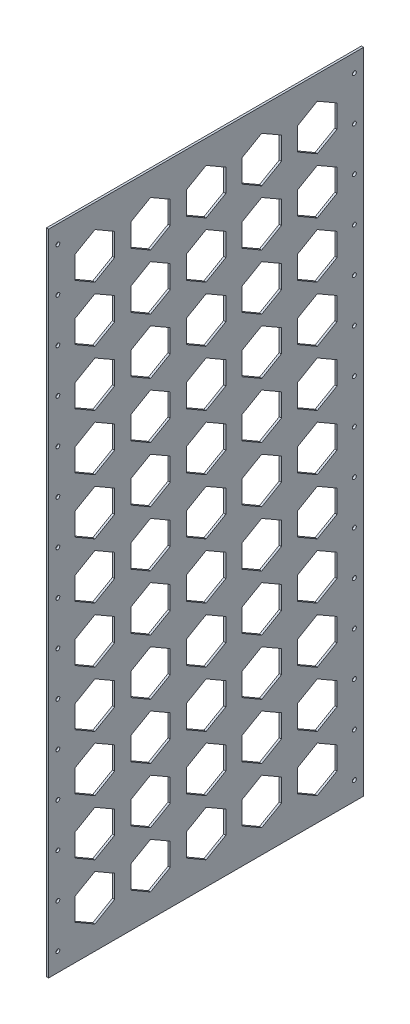
SolidWorks part; units mm, degrees
ref_plane "Front" through (0, 0, 0) normal (0, 0, 1) x (1, 0, 0)
ref_plane "Top" through (0, 0, 0) normal (0, 1, 0) x (1, 0, 0)
ref_plane "Right" through (0, 0, 0) normal (1, 0, 0) x (0, 0, -1)
sketch "Sketch1" plane through (0, 0, 0) normal (1, 0, 0) x (0, 0, -1)
  line L1 (0, 0) -> (431.8, 0)
  line L2 (0, 0) -> (0, 889)
  line L3 (0, 889) -> (431.8, 889)
  line L4 (431.8, 0) -> (431.8, 889)
  dimension "D1" = 889
  dimension "D2" = 431.8
extrude "Boss-Extrude1" add sketch "Sketch1" along normal blind 3
sketch "Sketch2" plane through (3, 0, 0) normal (1, 0, 0) x (0, 0, -1)
  line L1 (0, 0) -> (431.8, 0) construction
  line L2 (12.7, 25.4) -> (419.1, 25.4) construction
  line L3 (12.7, 25.4) -> (0, 25.4) construction
  line L4 (0, 889) -> (0, 0) construction
  line L5 (419.1, 25.4) -> (431.8, 25.4) construction
  line L6 (431.8, 0) -> (431.8, 889) construction
  line L7 (215.9, 25.4) -> (215.9, 0) construction
  circle A0 centre (12.7, 25.4) radius 2.667
  circle A1 centre (419.1, 25.4) radius 2.667
  circle A2 centre (419.1, 85.344) radius 2.667
  circle A3 centre (419.1, 145.288) radius 2.667
  circle A4 centre (419.1, 205.232) radius 2.667
  circle A5 centre (419.1, 265.176) radius 2.667
  circle A6 centre (419.1, 325.12) radius 2.667
  circle A7 centre (419.1, 385.064) radius 2.667
  circle A8 centre (419.1, 445.008) radius 2.667
  circle A9 centre (419.1, 504.952) radius 2.667
  circle A10 centre (419.1, 564.896) radius 2.667
  circle A11 centre (12.7, 85.344) radius 2.667
  circle A12 centre (12.7, 145.288) radius 2.667
  circle A13 centre (12.7, 205.232) radius 2.667
  circle A14 centre (12.7, 265.176) radius 2.667
  circle A15 centre (12.7, 325.12) radius 2.667
  circle A16 centre (12.7, 385.064) radius 2.667
  circle A17 centre (12.7, 445.008) radius 2.667
  circle A18 centre (12.7, 504.952) radius 2.667
  circle A19 centre (12.7, 564.896) radius 2.667
  circle A20 centre (12.7, 624.84) radius 2.667
  circle A21 centre (419.1, 624.84) radius 2.667
  circle A22 centre (12.7, 684.784) radius 2.667
  circle A23 centre (419.1, 684.784) radius 2.667
  circle A24 centre (12.7, 744.728) radius 2.667
  circle A25 centre (419.1, 744.728) radius 2.667
  circle A26 centre (12.7, 804.672) radius 2.667
  circle A27 centre (419.1, 804.672) radius 2.667
  circle A28 centre (12.7, 864.616) radius 2.667
  circle A29 centre (419.1, 864.616) radius 2.667
  dimension "D3" = 5.334
  dimension "D1" = 25.4
  dimension "D2" = 406.4
  dimension "D4" = 2
  dimension "D5" = 15
extrude "Cut-Extrude1" cut sketch "Sketch2" against normal up to next (3 mm away)
sketch "Sketch3" plane through (3, 0, 0) normal (1, 0, 0) x (0, 0, -1)
  line L0 (112.6706, 47.8946) -> (139.7, 32.2891)
  line L1 (36.4706, 47.8946) -> (63.5, 32.2891)
  line L2 (63.5, 32.2891) -> (90.5294, 47.8946)
  line L3 (90.5294, 47.8946) -> (90.5294, 79.1054)
  line L4 (90.5294, 79.1054) -> (63.5, 94.7109)
  line L5 (63.5, 94.7109) -> (36.4706, 79.1054)
  line L6 (36.4706, 79.1054) -> (36.4706, 47.8946)
  line L7 (139.7, 32.2891) -> (166.7294, 47.8946)
  line L8 (166.7294, 47.8946) -> (166.7294, 79.1054)
  line L9 (166.7294, 79.1054) -> (139.7, 94.7109)
  line L10 (139.7, 94.7109) -> (112.6706, 79.1054)
  line L11 (112.6706, 79.1054) -> (112.6706, 47.8946)
  line L12 (188.8706, 47.8946) -> (215.9, 32.2891)
  line L13 (215.9, 32.2891) -> (242.9294, 47.8946)
  line L14 (242.9294, 47.8946) -> (242.9294, 79.1054)
  line L15 (242.9294, 79.1054) -> (215.9, 94.7109)
  line L16 (215.9, 94.7109) -> (188.8706, 79.1054)
  line L17 (188.8706, 79.1054) -> (188.8706, 47.8946)
  line L18 (265.0706, 47.8946) -> (292.1, 32.2891)
  line L19 (292.1, 32.2891) -> (319.1294, 47.8946)
  line L20 (319.1294, 47.8946) -> (319.1294, 79.1054)
  line L21 (319.1294, 79.1054) -> (292.1, 94.7109)
  line L22 (292.1, 94.7109) -> (265.0706, 79.1054)
  line L23 (265.0706, 79.1054) -> (265.0706, 47.8946)
  line L24 (341.2706, 47.8946) -> (368.3, 32.2891)
  line L25 (368.3, 32.2891) -> (395.3294, 47.8946)
  line L26 (395.3294, 47.8946) -> (395.3294, 79.1054)
  line L27 (395.3294, 79.1054) -> (368.3, 94.7109)
  line L28 (368.3, 94.7109) -> (341.2706, 79.1054)
  line L29 (341.2706, 79.1054) -> (341.2706, 47.8946)
  line L30 (112.6706, 124.0946) -> (139.7, 108.4891)
  line L31 (139.7, 108.4891) -> (166.7294, 124.0946)
  line L32 (166.7294, 124.0946) -> (166.7294, 155.3054)
  line L33 (166.7294, 155.3054) -> (139.7, 170.9109)
  line L34 (139.7, 170.9109) -> (112.6706, 155.3054)
  line L35 (112.6706, 155.3054) -> (112.6706, 124.0946)
  line L36 (188.8706, 124.0946) -> (215.9, 108.4891)
  line L37 (215.9, 108.4891) -> (242.9294, 124.0946)
  line L38 (242.9294, 124.0946) -> (242.9294, 155.3054)
  line L39 (242.9294, 155.3054) -> (215.9, 170.9109)
  line L40 (215.9, 170.9109) -> (188.8706, 155.3054)
  line L41 (188.8706, 155.3054) -> (188.8706, 124.0946)
  line L42 (265.0706, 124.0946) -> (292.1, 108.4891)
  line L43 (292.1, 108.4891) -> (319.1294, 124.0946)
  line L44 (319.1294, 124.0946) -> (319.1294, 155.3054)
  line L45 (319.1294, 155.3054) -> (292.1, 170.9109)
  line L46 (292.1, 170.9109) -> (265.0706, 155.3054)
  line L47 (265.0706, 155.3054) -> (265.0706, 124.0946)
  line L48 (341.2706, 124.0946) -> (368.3, 108.4891)
  line L49 (368.3, 108.4891) -> (395.3294, 124.0946)
  line L50 (395.3294, 124.0946) -> (395.3294, 155.3054)
  line L51 (395.3294, 155.3054) -> (368.3, 170.9109)
  line L52 (368.3, 170.9109) -> (341.2706, 155.3054)
  line L53 (341.2706, 155.3054) -> (341.2706, 124.0946)
  line L54 (112.6706, 200.2946) -> (139.7, 184.6891)
  line L55 (139.7, 184.6891) -> (166.7294, 200.2946)
  line L56 (166.7294, 200.2946) -> (166.7294, 231.5054)
  line L57 (166.7294, 231.5054) -> (139.7, 247.1109)
  line L58 (139.7, 247.1109) -> (112.6706, 231.5054)
  line L59 (112.6706, 231.5054) -> (112.6706, 200.2946)
  line L60 (188.8706, 200.2946) -> (215.9, 184.6891)
  line L61 (215.9, 184.6891) -> (242.9294, 200.2946)
  line L62 (242.9294, 200.2946) -> (242.9294, 231.5054)
  line L63 (242.9294, 231.5054) -> (215.9, 247.1109)
  line L64 (215.9, 247.1109) -> (188.8706, 231.5054)
  line L65 (188.8706, 231.5054) -> (188.8706, 200.2946)
  line L66 (265.0706, 200.2946) -> (292.1, 184.6891)
  line L67 (292.1, 184.6891) -> (319.1294, 200.2946)
  line L68 (319.1294, 200.2946) -> (319.1294, 231.5054)
  line L69 (319.1294, 231.5054) -> (292.1, 247.1109)
  line L70 (292.1, 247.1109) -> (265.0706, 231.5054)
  line L71 (265.0706, 231.5054) -> (265.0706, 200.2946)
  line L72 (341.2706, 200.2946) -> (368.3, 184.6891)
  line L73 (368.3, 184.6891) -> (395.3294, 200.2946)
  line L74 (395.3294, 200.2946) -> (395.3294, 231.5054)
  line L75 (395.3294, 231.5054) -> (368.3, 247.1109)
  line L76 (368.3, 247.1109) -> (341.2706, 231.5054)
  line L77 (341.2706, 231.5054) -> (341.2706, 200.2946)
  line L78 (112.6706, 276.4946) -> (139.7, 260.8891)
  line L79 (139.7, 260.8891) -> (166.7294, 276.4946)
  line L80 (166.7294, 276.4946) -> (166.7294, 307.7054)
  line L81 (166.7294, 307.7054) -> (139.7, 323.3109)
  line L82 (139.7, 323.3109) -> (112.6706, 307.7054)
  line L83 (112.6706, 307.7054) -> (112.6706, 276.4946)
  line L84 (188.8706, 276.4946) -> (215.9, 260.8891)
  line L85 (215.9, 260.8891) -> (242.9294, 276.4946)
  line L86 (242.9294, 276.4946) -> (242.9294, 307.7054)
  line L87 (242.9294, 307.7054) -> (215.9, 323.3109)
  line L88 (215.9, 323.3109) -> (188.8706, 307.7054)
  line L89 (188.8706, 307.7054) -> (188.8706, 276.4946)
  line L90 (265.0706, 276.4946) -> (292.1, 260.8891)
  line L91 (292.1, 260.8891) -> (319.1294, 276.4946)
  line L92 (319.1294, 276.4946) -> (319.1294, 307.7054)
  line L93 (319.1294, 307.7054) -> (292.1, 323.3109)
  line L94 (292.1, 323.3109) -> (265.0706, 307.7054)
  line L95 (265.0706, 307.7054) -> (265.0706, 276.4946)
  line L96 (341.2706, 276.4946) -> (368.3, 260.8891)
  line L97 (368.3, 260.8891) -> (395.3294, 276.4946)
  line L98 (395.3294, 276.4946) -> (395.3294, 307.7054)
  line L99 (395.3294, 307.7054) -> (368.3, 323.3109)
  line L100 (368.3, 323.3109) -> (341.2706, 307.7054)
  line L101 (341.2706, 307.7054) -> (341.2706, 276.4946)
  line L102 (112.6706, 352.6946) -> (139.7, 337.0891)
  line L103 (139.7, 337.0891) -> (166.7294, 352.6946)
  line L104 (166.7294, 352.6946) -> (166.7294, 383.9054)
  line L105 (166.7294, 383.9054) -> (139.7, 399.5109)
  line L106 (139.7, 399.5109) -> (112.6706, 383.9054)
  line L107 (112.6706, 383.9054) -> (112.6706, 352.6946)
  line L108 (188.8706, 352.6946) -> (215.9, 337.0891)
  line L109 (215.9, 337.0891) -> (242.9294, 352.6946)
  line L110 (242.9294, 352.6946) -> (242.9294, 383.9054)
  line L111 (242.9294, 383.9054) -> (215.9, 399.5109)
  line L112 (215.9, 399.5109) -> (188.8706, 383.9054)
  line L113 (188.8706, 383.9054) -> (188.8706, 352.6946)
  line L114 (265.0706, 352.6946) -> (292.1, 337.0891)
  line L115 (292.1, 337.0891) -> (319.1294, 352.6946)
  line L116 (319.1294, 352.6946) -> (319.1294, 383.9054)
  line L117 (319.1294, 383.9054) -> (292.1, 399.5109)
  line L118 (292.1, 399.5109) -> (265.0706, 383.9054)
  line L119 (265.0706, 383.9054) -> (265.0706, 352.6946)
  line L120 (341.2706, 352.6946) -> (368.3, 337.0891)
  line L121 (368.3, 337.0891) -> (395.3294, 352.6946)
  line L122 (395.3294, 352.6946) -> (395.3294, 383.9054)
  line L123 (395.3294, 383.9054) -> (368.3, 399.5109)
  line L124 (368.3, 399.5109) -> (341.2706, 383.9054)
  line L125 (341.2706, 383.9054) -> (341.2706, 352.6946)
  line L126 (112.6706, 428.8946) -> (139.7, 413.2891)
  line L127 (139.7, 413.2891) -> (166.7294, 428.8946)
  line L128 (166.7294, 428.8946) -> (166.7294, 460.1054)
  line L129 (166.7294, 460.1054) -> (139.7, 475.7109)
  line L130 (139.7, 475.7109) -> (112.6706, 460.1054)
  line L131 (112.6706, 460.1054) -> (112.6706, 428.8946)
  line L132 (188.8706, 428.8946) -> (215.9, 413.2891)
  line L133 (215.9, 413.2891) -> (242.9294, 428.8946)
  line L134 (242.9294, 428.8946) -> (242.9294, 460.1054)
  line L135 (242.9294, 460.1054) -> (215.9, 475.7109)
  line L136 (215.9, 475.7109) -> (188.8706, 460.1054)
  line L137 (188.8706, 460.1054) -> (188.8706, 428.8946)
  line L138 (265.0706, 428.8946) -> (292.1, 413.2891)
  line L139 (292.1, 413.2891) -> (319.1294, 428.8946)
  line L140 (319.1294, 428.8946) -> (319.1294, 460.1054)
  line L141 (319.1294, 460.1054) -> (292.1, 475.7109)
  line L142 (292.1, 475.7109) -> (265.0706, 460.1054)
  line L143 (265.0706, 460.1054) -> (265.0706, 428.8946)
  line L144 (341.2706, 428.8946) -> (368.3, 413.2891)
  line L145 (368.3, 413.2891) -> (395.3294, 428.8946)
  line L146 (395.3294, 428.8946) -> (395.3294, 460.1054)
  line L147 (395.3294, 460.1054) -> (368.3, 475.7109)
  line L148 (368.3, 475.7109) -> (341.2706, 460.1054)
  line L149 (341.2706, 460.1054) -> (341.2706, 428.8946)
  line L150 (112.6706, 505.0946) -> (139.7, 489.4891)
  line L151 (139.7, 489.4891) -> (166.7294, 505.0946)
  line L152 (166.7294, 505.0946) -> (166.7294, 536.3054)
  line L153 (166.7294, 536.3054) -> (139.7, 551.9109)
  line L154 (139.7, 551.9109) -> (112.6706, 536.3054)
  line L155 (112.6706, 536.3054) -> (112.6706, 505.0946)
  line L156 (188.8706, 505.0946) -> (215.9, 489.4891)
  line L157 (215.9, 489.4891) -> (242.9294, 505.0946)
  line L158 (242.9294, 505.0946) -> (242.9294, 536.3054)
  line L159 (242.9294, 536.3054) -> (215.9, 551.9109)
  line L160 (215.9, 551.9109) -> (188.8706, 536.3054)
  line L161 (188.8706, 536.3054) -> (188.8706, 505.0946)
  line L162 (265.0706, 505.0946) -> (292.1, 489.4891)
  line L163 (292.1, 489.4891) -> (319.1294, 505.0946)
  line L164 (319.1294, 505.0946) -> (319.1294, 536.3054)
  line L165 (319.1294, 536.3054) -> (292.1, 551.9109)
  line L166 (292.1, 551.9109) -> (265.0706, 536.3054)
  line L167 (265.0706, 536.3054) -> (265.0706, 505.0946)
  line L168 (341.2706, 505.0946) -> (368.3, 489.4891)
  line L169 (368.3, 489.4891) -> (395.3294, 505.0946)
  line L170 (395.3294, 505.0946) -> (395.3294, 536.3054)
  line L171 (395.3294, 536.3054) -> (368.3, 551.9109)
  line L172 (368.3, 551.9109) -> (341.2706, 536.3054)
  line L173 (341.2706, 536.3054) -> (341.2706, 505.0946)
  line L174 (112.6706, 581.2946) -> (139.7, 565.6891)
  line L175 (139.7, 565.6891) -> (166.7294, 581.2946)
  line L176 (166.7294, 581.2946) -> (166.7294, 612.5054)
  line L177 (166.7294, 612.5054) -> (139.7, 628.1109)
  line L178 (139.7, 628.1109) -> (112.6706, 612.5054)
  line L179 (112.6706, 612.5054) -> (112.6706, 581.2946)
  line L180 (188.8706, 581.2946) -> (215.9, 565.6891)
  line L181 (215.9, 565.6891) -> (242.9294, 581.2946)
  line L182 (242.9294, 581.2946) -> (242.9294, 612.5054)
  line L183 (242.9294, 612.5054) -> (215.9, 628.1109)
  line L184 (215.9, 628.1109) -> (188.8706, 612.5054)
  line L185 (188.8706, 612.5054) -> (188.8706, 581.2946)
  line L186 (265.0706, 581.2946) -> (292.1, 565.6891)
  line L187 (292.1, 565.6891) -> (319.1294, 581.2946)
  line L188 (319.1294, 581.2946) -> (319.1294, 612.5054)
  line L189 (319.1294, 612.5054) -> (292.1, 628.1109)
  line L190 (292.1, 628.1109) -> (265.0706, 612.5054)
  line L191 (265.0706, 612.5054) -> (265.0706, 581.2946)
  line L192 (341.2706, 581.2946) -> (368.3, 565.6891)
  line L193 (368.3, 565.6891) -> (395.3294, 581.2946)
  line L194 (395.3294, 581.2946) -> (395.3294, 612.5054)
  line L195 (395.3294, 612.5054) -> (368.3, 628.1109)
  line L196 (368.3, 628.1109) -> (341.2706, 612.5054)
  line L197 (341.2706, 612.5054) -> (341.2706, 581.2946)
  line L198 (112.6706, 657.4946) -> (139.7, 641.8891)
  line L199 (139.7, 641.8891) -> (166.7294, 657.4946)
  line L200 (166.7294, 657.4946) -> (166.7294, 688.7054)
  line L201 (166.7294, 688.7054) -> (139.7, 704.3109)
  line L202 (139.7, 704.3109) -> (112.6706, 688.7054)
  line L203 (112.6706, 688.7054) -> (112.6706, 657.4946)
  line L204 (188.8706, 657.4946) -> (215.9, 641.8891)
  line L205 (215.9, 641.8891) -> (242.9294, 657.4946)
  line L206 (242.9294, 657.4946) -> (242.9294, 688.7054)
  line L207 (242.9294, 688.7054) -> (215.9, 704.3109)
  line L208 (215.9, 704.3109) -> (188.8706, 688.7054)
  line L209 (188.8706, 688.7054) -> (188.8706, 657.4946)
  line L210 (265.0706, 657.4946) -> (292.1, 641.8891)
  line L211 (292.1, 641.8891) -> (319.1294, 657.4946)
  line L212 (319.1294, 657.4946) -> (319.1294, 688.7054)
  line L213 (319.1294, 688.7054) -> (292.1, 704.3109)
  line L214 (292.1, 704.3109) -> (265.0706, 688.7054)
  line L215 (265.0706, 688.7054) -> (265.0706, 657.4946)
  line L216 (341.2706, 657.4946) -> (368.3, 641.8891)
  line L217 (368.3, 641.8891) -> (395.3294, 657.4946)
  line L218 (395.3294, 657.4946) -> (395.3294, 688.7054)
  line L219 (395.3294, 688.7054) -> (368.3, 704.3109)
  line L220 (368.3, 704.3109) -> (341.2706, 688.7054)
  line L221 (341.2706, 688.7054) -> (341.2706, 657.4946)
  line L222 (112.6706, 733.6946) -> (139.7, 718.0891)
  line L223 (139.7, 718.0891) -> (166.7294, 733.6946)
  line L224 (166.7294, 733.6946) -> (166.7294, 764.9054)
  line L225 (166.7294, 764.9054) -> (139.7, 780.5109)
  line L226 (139.7, 780.5109) -> (112.6706, 764.9054)
  line L227 (112.6706, 764.9054) -> (112.6706, 733.6946)
  line L228 (188.8706, 733.6946) -> (215.9, 718.0891)
  line L229 (215.9, 718.0891) -> (242.9294, 733.6946)
  line L230 (242.9294, 733.6946) -> (242.9294, 764.9054)
  line L231 (242.9294, 764.9054) -> (215.9, 780.5109)
  line L232 (215.9, 780.5109) -> (188.8706, 764.9054)
  line L233 (188.8706, 764.9054) -> (188.8706, 733.6946)
  line L234 (265.0706, 733.6946) -> (292.1, 718.0891)
  line L235 (292.1, 718.0891) -> (319.1294, 733.6946)
  line L236 (319.1294, 733.6946) -> (319.1294, 764.9054)
  line L237 (319.1294, 764.9054) -> (292.1, 780.5109)
  line L238 (292.1, 780.5109) -> (265.0706, 764.9054)
  line L239 (265.0706, 764.9054) -> (265.0706, 733.6946)
  line L240 (341.2706, 733.6946) -> (368.3, 718.0891)
  line L241 (368.3, 718.0891) -> (395.3294, 733.6946)
  line L242 (395.3294, 733.6946) -> (395.3294, 764.9054)
  line L243 (395.3294, 764.9054) -> (368.3, 780.5109)
  line L244 (368.3, 780.5109) -> (341.2706, 764.9054)
  line L245 (341.2706, 764.9054) -> (341.2706, 733.6946)
  line L246 (112.6706, 809.8946) -> (139.7, 794.2891)
  line L247 (139.7, 794.2891) -> (166.7294, 809.8946)
  line L248 (166.7294, 809.8946) -> (166.7294, 841.1054)
  line L249 (166.7294, 841.1054) -> (139.7, 856.7109)
  line L250 (139.7, 856.7109) -> (112.6706, 841.1054)
  line L251 (112.6706, 841.1054) -> (112.6706, 809.8946)
  line L252 (188.8706, 809.8946) -> (215.9, 794.2891)
  line L253 (215.9, 794.2891) -> (242.9294, 809.8946)
  line L254 (242.9294, 809.8946) -> (242.9294, 841.1054)
  line L255 (242.9294, 841.1054) -> (215.9, 856.7109)
  line L256 (215.9, 856.7109) -> (188.8706, 841.1054)
  line L257 (188.8706, 841.1054) -> (188.8706, 809.8946)
  line L258 (265.0706, 809.8946) -> (292.1, 794.2891)
  line L259 (292.1, 794.2891) -> (319.1294, 809.8946)
  line L260 (319.1294, 809.8946) -> (319.1294, 841.1054)
  line L261 (319.1294, 841.1054) -> (292.1, 856.7109)
  line L262 (292.1, 856.7109) -> (265.0706, 841.1054)
  line L263 (265.0706, 841.1054) -> (265.0706, 809.8946)
  line L264 (341.2706, 809.8946) -> (368.3, 794.2891)
  line L265 (368.3, 794.2891) -> (395.3294, 809.8946)
  line L266 (395.3294, 809.8946) -> (395.3294, 841.1054)
  line L267 (395.3294, 841.1054) -> (368.3, 856.7109)
  line L268 (368.3, 856.7109) -> (341.2706, 841.1054)
  line L269 (341.2706, 841.1054) -> (341.2706, 809.8946)
  line L270 (36.4706, 124.0946) -> (63.5, 108.4891)
  line L271 (63.5, 108.4891) -> (90.5294, 124.0946)
  line L272 (90.5294, 124.0946) -> (90.5294, 155.3054)
  line L273 (90.5294, 155.3054) -> (63.5, 170.9109)
  line L274 (63.5, 170.9109) -> (36.4706, 155.3054)
  line L275 (36.4706, 155.3054) -> (36.4706, 124.0946)
  line L276 (36.4706, 200.2946) -> (63.5, 184.6891)
  line L277 (63.5, 184.6891) -> (90.5294, 200.2946)
  line L278 (90.5294, 200.2946) -> (90.5294, 231.5054)
  line L279 (90.5294, 231.5054) -> (63.5, 247.1109)
  line L280 (63.5, 247.1109) -> (36.4706, 231.5054)
  line L281 (36.4706, 231.5054) -> (36.4706, 200.2946)
  line L282 (36.4706, 276.4946) -> (63.5, 260.8891)
  line L283 (63.5, 260.8891) -> (90.5294, 276.4946)
  line L284 (90.5294, 276.4946) -> (90.5294, 307.7054)
  line L285 (90.5294, 307.7054) -> (63.5, 323.3109)
  line L286 (63.5, 323.3109) -> (36.4706, 307.7054)
  line L287 (36.4706, 307.7054) -> (36.4706, 276.4946)
  line L288 (36.4706, 352.6946) -> (63.5, 337.0891)
  line L289 (63.5, 337.0891) -> (90.5294, 352.6946)
  line L290 (90.5294, 352.6946) -> (90.5294, 383.9054)
  line L291 (90.5294, 383.9054) -> (63.5, 399.5109)
  line L292 (63.5, 399.5109) -> (36.4706, 383.9054)
  line L293 (36.4706, 383.9054) -> (36.4706, 352.6946)
  line L294 (36.4706, 428.8946) -> (63.5, 413.2891)
  line L295 (63.5, 413.2891) -> (90.5294, 428.8946)
  line L296 (90.5294, 428.8946) -> (90.5294, 460.1054)
  line L297 (90.5294, 460.1054) -> (63.5, 475.7109)
  line L298 (63.5, 475.7109) -> (36.4706, 460.1054)
  line L299 (36.4706, 460.1054) -> (36.4706, 428.8946)
  line L300 (36.4706, 505.0946) -> (63.5, 489.4891)
  line L301 (63.5, 489.4891) -> (90.5294, 505.0946)
  line L302 (90.5294, 505.0946) -> (90.5294, 536.3054)
  line L303 (90.5294, 536.3054) -> (63.5, 551.9109)
  line L304 (63.5, 551.9109) -> (36.4706, 536.3054)
  line L305 (36.4706, 536.3054) -> (36.4706, 505.0946)
  line L306 (36.4706, 581.2946) -> (63.5, 565.6891)
  line L307 (63.5, 565.6891) -> (90.5294, 581.2946)
  line L308 (90.5294, 581.2946) -> (90.5294, 612.5054)
  line L309 (90.5294, 612.5054) -> (63.5, 628.1109)
  line L310 (63.5, 628.1109) -> (36.4706, 612.5054)
  line L311 (36.4706, 612.5054) -> (36.4706, 581.2946)
  line L312 (36.4706, 657.4946) -> (63.5, 641.8891)
  line L313 (63.5, 641.8891) -> (90.5294, 657.4946)
  line L314 (90.5294, 657.4946) -> (90.5294, 688.7054)
  line L315 (90.5294, 688.7054) -> (63.5, 704.3109)
  line L316 (63.5, 704.3109) -> (36.4706, 688.7054)
  line L317 (36.4706, 688.7054) -> (36.4706, 657.4946)
  line L318 (36.4706, 733.6946) -> (63.5, 718.0891)
  line L319 (63.5, 718.0891) -> (90.5294, 733.6946)
  line L320 (90.5294, 733.6946) -> (90.5294, 764.9054)
  line L321 (90.5294, 764.9054) -> (63.5, 780.5109)
  line L322 (63.5, 780.5109) -> (36.4706, 764.9054)
  line L323 (36.4706, 764.9054) -> (36.4706, 733.6946)
  line L324 (36.4706, 809.8946) -> (63.5, 794.2891)
  line L325 (63.5, 794.2891) -> (90.5294, 809.8946)
  line L326 (90.5294, 809.8946) -> (90.5294, 841.1054)
  line L327 (90.5294, 841.1054) -> (63.5, 856.7109)
  line L328 (63.5, 856.7109) -> (36.4706, 841.1054)
  line L329 (36.4706, 841.1054) -> (36.4706, 809.8946)
  line L330 (63.5, 63.5) -> (0, 63.5) construction
  line L331 (0, 889) -> (0, 0) construction
  line L332 (368.3, 63.5) -> (431.8, 63.5) construction
  line L333 (431.8, 0) -> (431.8, 889) construction
  line L334 (63.5, 63.5) -> (63.5, 0) construction
  line L335 (0, 0) -> (431.8, 0) construction
  line L336 (63.5, 825.5) -> (63.5, 889) construction
  line L337 (431.8, 889) -> (0, 889) construction
  circle A0 centre (63.5, 63.5) radius 27.0294 construction
  circle A1 centre (139.7, 63.5) radius 27.0294 construction
  circle A2 centre (215.9, 63.5) radius 27.0294 construction
  circle A3 centre (292.1, 63.5) radius 27.0294 construction
  circle A4 centre (368.3, 63.5) radius 27.0294 construction
  circle A5 centre (139.7, 139.7) radius 27.0294 construction
  circle A6 centre (215.9, 139.7) radius 27.0294 construction
  circle A7 centre (292.1, 139.7) radius 27.0294 construction
  circle A8 centre (368.3, 139.7) radius 27.0294 construction
  circle A9 centre (139.7, 215.9) radius 27.0294 construction
  circle A10 centre (215.9, 215.9) radius 27.0294 construction
  circle A11 centre (292.1, 215.9) radius 27.0294 construction
  circle A12 centre (368.3, 215.9) radius 27.0294 construction
  circle A13 centre (139.7, 292.1) radius 27.0294 construction
  circle A14 centre (215.9, 292.1) radius 27.0294 construction
  circle A15 centre (292.1, 292.1) radius 27.0294 construction
  circle A16 centre (368.3, 292.1) radius 27.0294 construction
  circle A17 centre (139.7, 368.3) radius 27.0294 construction
  circle A18 centre (215.9, 368.3) radius 27.0294 construction
  circle A19 centre (292.1, 368.3) radius 27.0294 construction
  circle A20 centre (368.3, 368.3) radius 27.0294 construction
  circle A21 centre (139.7, 444.5) radius 27.0294 construction
  circle A22 centre (215.9, 444.5) radius 27.0294 construction
  circle A23 centre (292.1, 444.5) radius 27.0294 construction
  circle A24 centre (368.3, 444.5) radius 27.0294 construction
  circle A25 centre (139.7, 520.7) radius 27.0294 construction
  circle A26 centre (215.9, 520.7) radius 27.0294 construction
  circle A27 centre (292.1, 520.7) radius 27.0294 construction
  circle A28 centre (368.3, 520.7) radius 27.0294 construction
  circle A29 centre (139.7, 596.9) radius 27.0294 construction
  circle A30 centre (215.9, 596.9) radius 27.0294 construction
  circle A31 centre (292.1, 596.9) radius 27.0294 construction
  circle A32 centre (368.3, 596.9) radius 27.0294 construction
  circle A33 centre (139.7, 673.1) radius 27.0294 construction
  circle A34 centre (215.9, 673.1) radius 27.0294 construction
  circle A35 centre (292.1, 673.1) radius 27.0294 construction
  circle A36 centre (368.3, 673.1) radius 27.0294 construction
  circle A37 centre (139.7, 749.3) radius 27.0294 construction
  circle A38 centre (215.9, 749.3) radius 27.0294 construction
  circle A39 centre (292.1, 749.3) radius 27.0294 construction
  circle A40 centre (368.3, 749.3) radius 27.0294 construction
  circle A41 centre (139.7, 825.5) radius 27.0294 construction
  circle A42 centre (215.9, 825.5) radius 27.0294 construction
  circle A43 centre (292.1, 825.5) radius 27.0294 construction
  circle A44 centre (368.3, 825.5) radius 27.0294 construction
  circle A45 centre (63.5, 139.7) radius 27.0294 construction
  circle A46 centre (63.5, 215.9) radius 27.0294 construction
  circle A47 centre (63.5, 292.1) radius 27.0294 construction
  circle A48 centre (63.5, 368.3) radius 27.0294 construction
  circle A49 centre (63.5, 444.5) radius 27.0294 construction
  circle A50 centre (63.5, 520.7) radius 27.0294 construction
  circle A51 centre (63.5, 596.9) radius 27.0294 construction
  circle A52 centre (63.5, 673.1) radius 27.0294 construction
  circle A53 centre (63.5, 749.3) radius 27.0294 construction
  circle A54 centre (63.5, 825.5) radius 27.0294 construction
  dimension "D1" = 5
  dimension "D2" = 11
extrude "Cut-Extrude2" cut sketch "Sketch3" against normal up to next (3 mm away)
